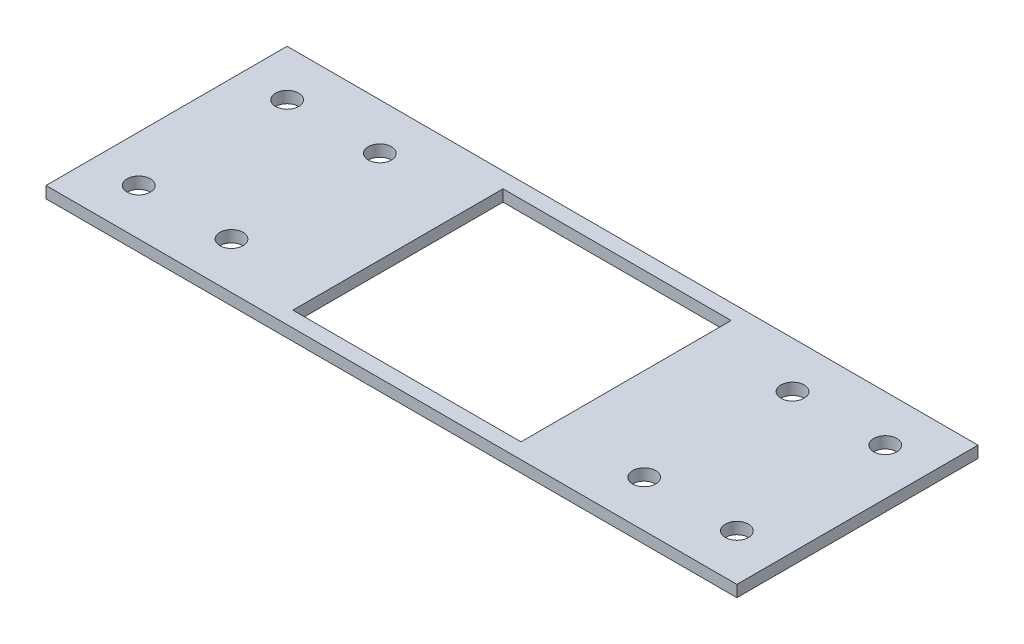
SolidWorks part; units mm, degrees
ref_plane "Front Plane" through (0, 0, 0) normal (0, 0, 1) x (1, 0, 0)
ref_plane "Top Plane" through (0, 0, 0) normal (0, 1, 0) x (1, 0, 0)
ref_plane "Right Plane" through (0, 0, 0) normal (1, 0, 0) x (0, 0, -1)
sketch "Sketch1" plane through (0, 0, 0) normal (0, 1, 0) x (1, 0, 0)
  line L1 (69.215, -33.02) -> (-69.215, -33.02)
  line L2 (69.215, -33.02) -> (69.215, 33.02)
  line L3 (69.215, 33.02) -> (-69.215, 33.02)
  line L4 (-69.215, -33.02) -> (-69.215, 33.02)
  line L5 (69.215, -33.02) -> (-69.215, 33.02) construction
  line L6 (69.215, 33.02) -> (-69.215, -33.02) construction
  point P0 (0, 0)
  dimension "D1" = 66.04
  dimension "D2" = 138.43
extrude "Boss-Extrude1" add sketch "Sketch1" along normal blind 25.4
sketch "Sketch2" plane through (-69.215, 0, 0) normal (-1, 0, 0) x (0, 0, 1)
  line L0 (-33.02, 25.4) -> (-33.02, 0) construction
  line L1 (33.02, 22.225) -> (-33.02, 22.225)
  line L2 (33.02, 22.225) -> (33.02, 0)
  line L3 (33.02, 0) -> (-33.02, 0)
  line L4 (-33.02, 22.225) -> (-33.02, 0)
  line L5 (33.02, 22.225) -> (-33.02, 0) construction
  line L6 (33.02, 0) -> (-33.02, 22.225) construction
  line L7 (33.02, 25.4) -> (33.02, 0) construction
  line L8 (-33.02, 25.4) -> (33.02, 25.4) construction
  line L9 (-33.02, 0) -> (33.02, 0) construction
  point P0 (0, 11.1125)
  dimension "D1" = 0
  dimension "D2" = 0
  dimension "D3" = 3.175
  dimension "D4" = 0
extrude "Cut-Extrude1" cut sketch "Sketch2" against normal up to next
sketch "Sketch3" plane through (0, 25.4, 0) normal (0, 1, 0) x (1, 0, 0)
  line L1 (69.215, 33.02) -> (-69.215, 33.02) construction
  line L2 (-69.215, -33.02) -> (69.215, -33.02) construction
  line L3 (-69.215, 33.02) -> (-69.215, -33.02) construction
  line L4 (-69.215, 0) -> (69.215, 0) construction
  line L5 (69.215, -33.02) -> (69.215, 33.02) construction
  line L6 (0, 33.02) -> (0, -33.02) construction
  circle A0 centre (-56.515, 20.32) radius 3.175
  circle A1 centre (-56.515, -20.32) radius 3.175
  circle A5 centre (56.515, -20.32) radius 3.175
  circle A6 centre (56.515, 20.32) radius 3.175
  dimension "D2" = 6.35
  dimension "D3" = 12.7
  dimension "D4" = 12.7
extrude "Cut-Extrude2" cut sketch "Sketch3" against normal through all
sketch "Sketch5" plane through (-69.215, 0, 0) normal (-1, 0, 0) x (0, 0, 1)
  line L4 (-33.02, 25.4) -> (-33.02, 22.225)
  line L5 (-33.02, 22.225) -> (33.02, 22.225)
  line L6 (33.02, 22.225) -> (33.02, 25.4)
  line L7 (33.02, 25.4) -> (-33.02, 25.4)
  line L8 (-33.02, 25.4) -> (-33.02, 22.225)
  line L9 (-33.02, 22.225) -> (33.02, 22.225)
  line L10 (33.02, 22.225) -> (33.02, 25.4)
  line L11 (33.02, 25.4) -> (-33.02, 25.4)
  dimension "D1" = 0
extrude "Boss-Extrude2" add sketch "Sketch5" along normal blind 25.4
sketch "Sketch7" plane through (69.215, 0, 0) normal (1, 0, 0) x (0, 0, -1)
  line L4 (-33.02, 25.4) -> (-33.02, 22.225)
  line L5 (-33.02, 22.225) -> (33.02, 22.225)
  line L6 (33.02, 22.225) -> (33.02, 25.4)
  line L7 (33.02, 25.4) -> (-33.02, 25.4)
  line L8 (-33.02, 25.4) -> (-33.02, 22.225)
  line L9 (-33.02, 22.225) -> (33.02, 22.225)
  line L10 (33.02, 22.225) -> (33.02, 25.4)
  line L11 (33.02, 25.4) -> (-33.02, 25.4)
  dimension "D1" = 0
extrude "Boss-Extrude3" add sketch "Sketch7" along normal blind 25.4
sketch "Sketch8" plane through (0, 25.4, 0) normal (0, 1, 0) x (1, 0, 0)
  line L0 (-69.215, -33.02) -> (-69.215, 33.02) construction
  line L1 (-94.615, -33.02) -> (94.615, -33.02) construction
  line L2 (94.615, 33.02) -> (-94.615, 33.02) construction
  line L3 (69.215, 33.02) -> (69.215, -33.02) construction
  line L4 (-94.615, -33.02) -> (-94.615, 33.02) construction
  line L5 (94.615, 33.02) -> (94.615, -33.02) construction
  line L6 (-94.615, 0) -> (94.615, 0) construction
  line L7 (0, 33.02) -> (0, -33.02) construction
  circle A0 centre (-81.915, 20.32) radius 3.175
  circle A1 centre (-81.915, -20.32) radius 3.175
  circle A2 centre (81.915, -20.32) radius 3.175
  circle A3 centre (81.915, 20.32) radius 3.175
  dimension "D3" = 6.35
  dimension "D4" = 12.7
  dimension "D5" = 12.7
  dimension "D1" = 25.4
  dimension "D2" = 25.4
extrude "Cut-Extrude3" cut sketch "Sketch8" against normal up to next
sketch "Sketch9" plane through (0, 25.4, 0) normal (0, 1, 0) x (1, 0, 0)
  line L1 (40.64, -28.7845) -> (-40.64, -28.7845)
  line L2 (40.64, -28.7845) -> (40.64, 28.7845)
  line L3 (40.64, 28.7845) -> (-40.64, 28.7845)
  line L4 (-40.64, -28.7845) -> (-40.64, 28.7845)
  line L5 (40.64, -28.7845) -> (-40.64, 28.7845) construction
  line L6 (40.64, 28.7845) -> (-40.64, -28.7845) construction
  line L7 (-40.64, -28.7845) -> (-31.242, -28.7845)
  line L8 (-40.64, -28.7845) -> (-40.64, 28.7845)
  line L9 (-40.64, 28.7845) -> (-31.242, 28.7845)
  line L10 (-31.242, -28.7845) -> (-31.242, 28.7845)
  line L11 (40.64, 28.7845) -> (31.242, 28.7845)
  line L12 (40.64, 28.7845) -> (40.64, -28.7845)
  line L13 (40.64, -28.7845) -> (31.242, -28.7845)
  line L14 (31.242, 28.7845) -> (31.242, -28.7845)
  point P0 (0, 0)
  dimension "D1" = 57.5689
  dimension "D2" = 81.28
  dimension "D3" = 9.398
  dimension "D4" = 9.398
extrude "Cut-Extrude4" cut sketch "Sketch9" against normal through all contours L14 L3 L10 L1 region at (0, 25.4, 0)
